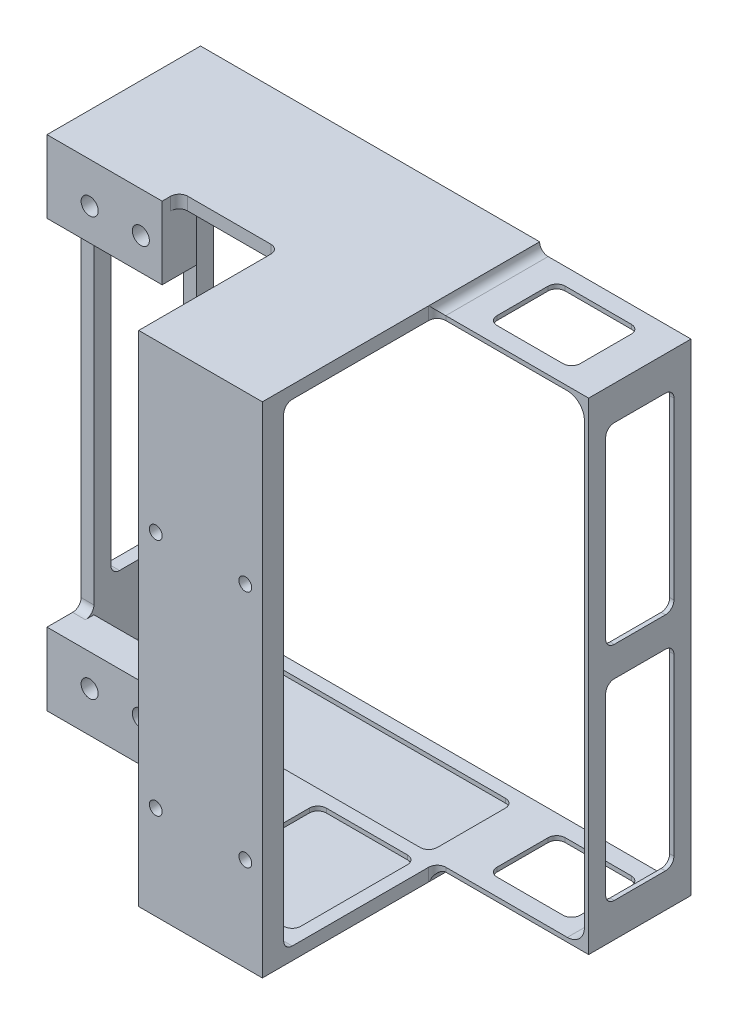
SolidWorks part; units mm, degrees
material "Bambu PETG HF"
ref_plane "Front Plane" through (0, 0, 0) normal (0, 0, 1) x (1, 0, 0)
ref_plane "Top Plane" through (0, 0, 0) normal (0, 1, 0) x (1, 0, 0)
ref_plane "Right Plane" through (0, 0, 0) normal (1, 0, 0) x (0, 0, -1)
sketch "Sketch2" plane through (0, 0, 0) normal (0, 0, 1) x (1, 0, 0)
  line L1 (-56.5, -56.5) -> (56.5, -56.5)
  line L2 (-56.5, -56.5) -> (-56.5, 56.5)
  line L3 (-56.5, 56.5) -> (56.5, 56.5)
  line L4 (56.5, -56.5) -> (56.5, 56.5)
  line L5 (-56.5, -56.5) -> (56.5, 56.5) construction
  line L6 (-56.5, 56.5) -> (56.5, -56.5) construction
  line L7 (-53.5, -53.5) -> (53.5, -53.5)
  line L8 (-53.5, -53.5) -> (-53.5, 53.5)
  line L9 (-53.5, 53.5) -> (53.5, 53.5)
  line L10 (53.5, -53.5) -> (53.5, 53.5)
  line L11 (-53.5, -53.5) -> (53.5, 53.5) construction
  line L12 (-53.5, 53.5) -> (53.5, -53.5) construction
  point P0 (0, 0)
  point P6 (0, 0)
  dimension "D1" = 3
  dimension "D2" = 107
  dimension "D4" = 107
extrude "Boss-Extrude1" add sketch "Sketch2" along normal blind 11
sketch "Sketch3" plane through (0, 0, 0) normal (0, 0, 1) x (1, 0, 0)
  line L0 (-56.5, 56.5) -> (-56.5, -56.5) construction
  line L2 (-56.5, 15) -> (-96.5, 15)
  line L3 (-56.5, 15) -> (-56.5, -15)
  line L4 (-56.5, -15) -> (-96.5, -15)
  line L5 (-96.5, 15) -> (-96.5, -15)
  point P6 (-56.5, 0)
  dimension "D1" = 30
  dimension "D2" = 40
extrude "Boss-Extrude2" add sketch "Sketch3" along normal blind 2
sketch "Sketch6" plane through (0, 0, 0) normal (0, 0, 1) x (1, 0, 0)
  line L0 (-56.5, -56.5) -> (56.5, -56.5) construction
  line L1 (-3, -56.5) -> (21, -56.5)
  line L2 (-3, -56.5) -> (-3, -58.5)
  line L3 (-3, -58.5) -> (21, -58.5)
  line L4 (21, -56.5) -> (21, -58.5)
  line L5 (-53.5, 0) -> (53.5, 0) construction
  line L6 (-53.5, 53.5) -> (-53.5, -53.5) construction
  line L7 (53.5, -53.5) -> (53.5, 53.5) construction
  line L8 (-3, 58.5) -> (21, 58.5)
  line L9 (21, 56.5) -> (21, 58.5)
  line L10 (-3, 56.5) -> (21, 56.5)
  line L11 (-3, 56.5) -> (-3, 58.5)
  line L12 (0, 0) -> (0, -53.5) construction
  line L13 (-53.5, -53.5) -> (53.5, -53.5) construction
  dimension "D1" = 2
  dimension "D2" = 24
  dimension "D3" = 3
extrude "Boss-Extrude5" add sketch "Sketch6" along normal blind 50 and the other way blind 10
sketch "Sketch8" plane through (0, 0, 50) normal (0, 0, 1) x (1, 0, 0)
  line L0 (-3, 58.5) -> (-8, 58.5)
  line L1 (-3, 58.5) -> (21, 58.5)
  line L3 (-3, -58.5) -> (21, -58.5)
  line L4 (21, 58.5) -> (21, -58.5)
  line L5 (-8, 58.5) -> (-8, -58.5)
  line L6 (-8, -58.5) -> (-3, -58.5)
  dimension "D1" = 24
  dimension "D2" = 5
extrude "Boss-Extrude6" add sketch "Sketch8" along normal blind 5
sketch "Sketch9" plane through (0, 0, 55) normal (0, 0, 1) x (1, 0, 0)
  line L0 (-3, 58.5) -> (-8, 58.5)
  line L5 (-3, -58.5) -> (21, -58.5)
  line L7 (21, 56.5) -> (21, 54.5)
  line L12 (-3, 58.5) -> (21, 58.5)
  line L14 (-8, 58.5) -> (-8, 43.5)
  line L15 (-8, 58.5) -> (-8, -58.5) construction
  line L16 (-8, 43.5) -> (21, 43.5)
  line L17 (21, -58.5) -> (21, 58.5) construction
  line L18 (21, 43.5) -> (21, 54.5)
  line L19 (45.8512, 0) -> (-63.6843, 0) construction
  line L20 (21, -43.5) -> (21, -54.5)
  line L21 (-8, -43.5) -> (21, -43.5)
  line L22 (-8, -58.5) -> (-8, -43.5)
  line L23 (-3, -58.5) -> (-8, -58.5)
  line L25 (21, -56.5) -> (21, -54.5)
  line L26 (21, 58.5) -> (21, 56.5)
  line L27 (21, -58.5) -> (21, -56.5)
  dimension "D1" = 15
extrude "Boss-Extrude7" add sketch "Sketch9" along normal blind 4
sketch "Sketch12" plane through (0, 0, 55) normal (0, 0, 1) x (1, 0, 0)
  line L0 (17, 19.5) -> (-4, 19.5) construction
  line L1 (17, -36.5) -> (-4, -36.5) construction
  line L2 (-8, 43.5) -> (-8, -43.5) construction
  line L4 (-8, -58.5) -> (21, -58.5) construction
  line L5 (6.5, 19.5) -> (6.5, -36.5) construction
  circle A0 centre (17, 19.5) radius 1.5
  circle A1 centre (-4, 19.5) radius 1.5
  circle A2 centre (17, -36.5) radius 1.5
  circle A3 centre (-4, -36.5) radius 1.5
  point P8 (6.5, -36.5)
  dimension "D1" = 56
  dimension "D2" = 21
  dimension "D3" = 22
  dimension "D4" = 4
extrude "Cut-Extrude1" cut sketch "Sketch12" against normal through all
sketch "Sketch17" plane through (-56.5, 0, 0) normal (-1, 0, 0) x (0, 0, 1)
  line L1 (-20.9734, 30.8852) -> (89.5007, 30.8852)
  line L2 (-20.9734, 30.8852) -> (-20.9734, -32.0731)
  line L3 (-20.9734, -32.0731) -> (89.5007, -32.0731)
  line L4 (89.5007, 30.8852) -> (89.5007, -32.0731)
extrude "removal of battery extension" cut sketch "Sketch17" along normal through all
sketch "Sketch18" plane through (0, 0, 0) normal (0, 0, -1) x (-1, 0, 0)
  line L1 (-56.5, -56.5) -> (56.5, -56.5)
  line L2 (-56.5, -56.5) -> (-56.5, 56.5)
  line L3 (-56.5, 56.5) -> (56.5, 56.5)
  line L4 (56.5, -56.5) -> (56.5, 56.5)
  line L5 (-56.5, -56.5) -> (56.5, 56.5) construction
  line L6 (-56.5, 56.5) -> (56.5, -56.5) construction
  line L7 (-53.5, -53.5) -> (53.5, -53.5)
  line L8 (-53.5, -53.5) -> (-53.5, 53.5)
  line L9 (-53.5, 53.5) -> (53.5, 53.5)
  line L10 (53.5, -53.5) -> (53.5, 53.5)
  line L11 (-53.5, -53.5) -> (53.5, 53.5) construction
  line L12 (-53.5, 53.5) -> (53.5, -53.5) construction
  point P0 (0, 0)
  point P7 (0, 0)
extrude "Extend walls" add sketch "Sketch18" along normal blind 10
sketch "Sketch22" plane through (0, 0, 11) normal (0, 0, 1) x (1, 0, 0)
  line L0 (21, 56.5) -> (-3, 56.5)
  line L1 (-3, 56.5) -> (-3, 53.5)
  line L2 (53.5, 53.5) -> (-53.5, 53.5) construction
  line L3 (-3, 53.5) -> (21, 53.5)
  line L4 (21, 53.5) -> (21, 56.5)
  line L5 (-3, -56.5) -> (21, -56.5)
  line L6 (21, -56.5) -> (21, -53.5)
  line L7 (-53.5, -53.5) -> (53.5, -53.5) construction
  line L8 (21, -53.5) -> (-3, -53.5)
  line L9 (-3, -53.5) -> (-3, -56.5)
extrude "Boss-Extrude10" add sketch "Sketch22" along normal up to next
sketch "Sketch23" plane through (0, 0, 11) normal (0, 0, 1) x (1, 0, 0)
  line L0 (21, -56.5) -> (21, -53.5)
  line L1 (21, -53.5) -> (53.5, -53.5)
  line L2 (53.5, -53.5) -> (53.5, 53.5)
  line L3 (53.5, 53.5) -> (21, 53.5)
  line L4 (21, 53.5) -> (21, 56.5)
  line L5 (21, 56.5) -> (56.5, 56.5)
  line L6 (56.5, 56.5) -> (56.5, -56.5)
  line L7 (56.5, -56.5) -> (21, -56.5)
  line L8 (-3, 53.5) -> (-3, 56.5)
  line L9 (-3, 56.5) -> (-56.5, 56.5)
  line L10 (-56.5, 56.5) -> (-56.5, -56.5)
  line L11 (-56.5, -56.5) -> (-3, -56.5)
  line L12 (-3, -56.5) -> (-3, -53.5)
  line L13 (-3, -53.5) -> (-53.5, -53.5)
  line L14 (-53.5, -53.5) -> (-53.5, 53.5)
  line L15 (-53.5, 53.5) -> (-3, 53.5)
extrude "Boss-Extrude11" add sketch "Sketch23" along normal blind 7
sketch "Sketch24" plane through (0, 0, 18) normal (0, 0, 1) x (1, 0, 0)
  line L0 (-56.5, 56.5) -> (-29.5, 56.5)
  line L1 (-3, 56.5) -> (-56.5, 56.5) construction
  line L2 (-29.5, 56.5) -> (-29.5, 41.5)
  line L3 (-29.5, 41.5) -> (-56.5, 41.5)
  line L4 (-56.5, 56.5) -> (-56.5, -56.5) construction
  line L5 (-56.5, 41.5) -> (-56.5, 56.5)
  line L6 (-108.2725, 0) -> (166.4714, 0) construction
  line L7 (-29.5, -41.5) -> (-56.5, -41.5)
  line L8 (-29.5, -56.5) -> (-29.5, -41.5)
  line L9 (-56.5, -56.5) -> (-29.5, -56.5)
  line L10 (-56.5, -41.5) -> (-56.5, -56.5)
  dimension "D1" = 15
  dimension "D2" = 27
extrude "Boss-Extrude12" add sketch "Sketch24" along normal blind 8
sketch "Sketch25" plane through (0, 0, 26) normal (0, 0, 1) x (1, 0, 0)
  line L0 (-58.2026, 49) -> (-24.3527, 49) construction
  line L1 (85.7624, 0) -> (-93.076, 0) construction
  line L3 (-56.5, 56.5) -> (-56.5, 41.5) construction
  circle A0 centre (-48.5, 49) radius 2
  circle A1 centre (-36.5, 49) radius 2
  circle A2 centre (-48.5, -49) radius 2
  circle A3 centre (-36.5, -49) radius 2
  dimension "D1" = 4
  dimension "D2" = 4
  dimension "D3" = 12
  dimension "D5" = 8
extrude "Cut-Extrude4" cut sketch "Sketch25" against normal blind 9
sketch "Sketch27" plane through (0, 56.5, 0) normal (0, 1, 0) x (1, 0, 0)
  line L0 (-29.5, -26) -> (-29.5, -18)
  line L1 (-29.5, -18) -> (-3, -18)
  line L2 (-3, -18) -> (-3, 10)
  line L3 (-3, 10) -> (-56.5, 10)
  line L4 (-56.5, 10) -> (-56.5, -26)
  line L5 (-56.5, -26) -> (-29.5, -26)
extrude "Boss-Extrude13" add sketch "Sketch27" along normal blind 2
sketch "Sketch28" plane through (0, -56.5, 0) normal (0, -1, 0) x (1, 0, 0)
  line L0 (-56.5, 26) -> (-56.5, -10)
  line L1 (-56.5, -10) -> (-3, -10)
  line L2 (-3, -10) -> (-3, 18)
  line L3 (-3, 18) -> (-29.5, 18)
  line L4 (-29.5, 18) -> (-29.5, 26)
  line L5 (-29.5, 26) -> (-56.5, 26)
extrude "Boss-Extrude14" add sketch "Sketch28" along normal blind 2
sketch "Sketch29" plane through (0, 0, 18) normal (0, 0, 1) x (1, 0, 0)
  line L0 (-3, 53.5) -> (-3, 58.5)
  line L1 (-3, 58.5) -> (-29.5, 58.5)
  line L2 (-29.5, 58.5) -> (-29.5, 53.5)
  line L3 (-29.5, 53.5) -> (-3, 53.5)
  line L4 (-79.818, 0) -> (91.158, 0) construction
  line L5 (-29.5, -58.5) -> (-29.5, -53.5)
  line L6 (-3, -58.5) -> (-29.5, -58.5)
  line L7 (-3, -53.5) -> (-3, -58.5)
  line L8 (-29.5, -53.5) -> (-3, -53.5)
extrude "Boss-Extrude15" add sketch "Sketch29" along normal blind 4
sketch "Sketch30" plane through (-56.5, 0, 0) normal (-1, 0, 0) x (0, 0, 1)
  line L0 (26, 58.5) -> (-10, 58.5)
  line L1 (-10, 58.5) -> (-10, -58.5)
  line L2 (-10, -58.5) -> (26, -58.5)
  line L3 (26, -58.5) -> (26, -41.5)
  line L4 (26, -41.5) -> (18, -41.5)
  line L5 (18, -41.5) -> (18, 41.5)
  line L6 (18, 41.5) -> (26, 41.5)
  line L7 (26, 41.5) -> (26, 58.5)
extrude "Boss-Extrude16" add sketch "Sketch30" along normal blind 2
sketch "Sketch31" plane through (0, 0, 50) normal (0, 0, -1) x (-1, 0, 0)
  line L0 (8, 58.5) -> (3, 58.5)
  line L1 (3, 58.5) -> (3, 53.5)
  line L2 (3, 53.5) -> (8, 53.5)
  line L3 (8, 58.5) -> (8, -58.5) construction
  line L4 (8, 53.5) -> (8, 58.5)
  line L5 (62.5415, 0) -> (-54.383, 0) construction
  line L6 (3, -53.5) -> (8, -53.5)
  line L7 (3, -58.5) -> (3, -53.5)
  line L8 (8, -58.5) -> (3, -58.5)
  line L9 (8, -53.5) -> (8, -58.5)
extrude "Boss-Extrude17" add sketch "Sketch31" along normal up to next
sketch "Sketch32" plane through (0, 0, 18) normal (0, 0, 1) x (1, 0, 0)
  line L0 (21, -56.5) -> (21, -53.5)
  line L1 (21, -53.5) -> (53.5, -53.5)
  line L2 (53.5, -53.5) -> (53.5, 53.5)
  line L3 (53.5, 53.5) -> (21, 53.5)
  line L4 (21, 53.5) -> (21, 56.5)
  line L5 (21, 56.5) -> (56.5, 56.5)
  line L6 (56.5, 56.5) -> (56.5, -56.5)
  line L7 (56.5, -56.5) -> (21, -56.5)
extrude "Cut-Extrude5" cut sketch "Sketch32" against normal blind 4
sketch "Sketch33" plane through (0, -43.5, 0) normal (0, 1, 0) x (1, 0, 0)
  line L0 (21, -59) -> (21, -55)
  line L1 (21, -55) -> (-8, -55)
  line L2 (-8, -55) -> (-8, -59)
  line L3 (-8, -59) -> (21, -59)
extrude "Cut-Extrude6" cut sketch "Sketch33" against normal mid plane 220
sketch "Sketch34" plane through (56.5, 0, 0) normal (1, 0, 0) x (0, 0, -1)
  line L0 (30.1438, 0) -> (-36.494, 0) construction
  line L1 (-2, -56.5) -> (-2, 56.5) construction
  line L2 (-14, -56.5) -> (10, -56.5) construction
  line L3 (-14, 56.5) -> (10, 56.5) construction
  line L4 (-2, -48.5) -> (-10, -48.5)
  line L5 (-10, -48.5) -> (-10, -3.5)
  line L6 (-10, -3.5) -> (6, -3.5)
  line L7 (6, -3.5) -> (6, -48.5)
  line L8 (6, -48.5) -> (-2, -48.5)
  line L9 (-14, -56.5) -> (-14, 56.5) construction
  line L10 (10, 56.5) -> (10, -56.5) construction
  line L11 (6, 3.5) -> (6, 48.5)
  line L12 (6, 48.5) -> (-2, 48.5)
  line L13 (-2, 48.5) -> (-10, 48.5)
  line L14 (-10, 48.5) -> (-10, 3.5)
  line L15 (-10, 3.5) -> (6, 3.5)
  dimension "D1" = 45
  dimension "D2" = 8
  dimension "D3" = 4
  dimension "D4" = 4
extrude "Cut-Extrude7" cut sketch "Sketch34" against normal blind 10
sketch "Sketch35" plane through (0, -56.5, 0) normal (0, -1, 0) x (1, 0, 0)
  line L0 (56.5, 2) -> (21, 2) construction
  line L1 (56.5, 14) -> (56.5, -10) construction
  line L2 (21, -10) -> (21, 14) construction
  line L3 (38.75, 14) -> (38.75, -10) construction
  line L4 (21, 14) -> (56.5, 14) construction
  line L5 (56.5, -10) -> (21, -10) construction
  line L7 (29, 10) -> (48.5, 10)
  line L8 (29, 10) -> (29, -6)
  line L9 (29, -6) -> (48.5, -6)
  line L10 (48.5, 10) -> (48.5, -6)
  line L11 (29, 10) -> (48.5, -6) construction
  line L12 (29, -6) -> (48.5, 10) construction
  point P12 (38.75, 2)
  dimension "D1" = 8
  dimension "D2" = 4
extrude "Cut-Extrude8" cut sketch "Sketch35" against normal through all
sketch "Sketch37" plane through (-29.5, 0, 0) normal (1, 0, 0) x (0, 0, -1)
  line L0 (-26, 41.5) -> (-26, 58.5) construction
  line L1 (-22, -58.5) -> (-26, -58.5)
  line L2 (-22, -58.5) -> (-22, 58.5)
  line L3 (-22, 58.5) -> (-26, 58.5)
  line L4 (-26, -58.5) -> (-26, 58.5)
  line L5 (-26, 58.5) -> (-22, 58.5) construction
extrude "Cut-Extrude13" cut sketch "Sketch37" against normal blind 2
sketch "Sketch38" plane through (0, 0, 22) normal (0, 0, 1) x (1, 0, 0)
  line L0 (-29.5, -41.5) -> (-31.5, -41.5)
  line L1 (-29.5, -41.5) -> (-29.5, -53.5)
  line L2 (-29.5, -53.5) -> (-31.5, -53.5)
  line L3 (-31.5, -58.5) -> (-31.5, -41.5) construction
  line L4 (-31.5, -53.5) -> (-31.5, -41.5)
  line L5 (-67.9912, 0) -> (83.8266, 0) construction
  line L6 (-29.5, 53.5) -> (-31.5, 53.5)
  line L7 (-31.5, 53.5) -> (-31.5, 41.5)
  line L8 (-29.5, 41.5) -> (-31.5, 41.5)
  line L9 (-29.5, 41.5) -> (-29.5, 53.5)
extrude "Cut-Extrude14" cut sketch "Sketch38" against normal blind 10
fillet "Fillet1" radius 2 36 edges at (-42.5, 53.5, 18) (-42.5, -53.5, 18) (-56, -41.5, 18) (-56, 41.5, 18) (-31.5, 53.5, 20) (-31.5, 56, 22) (-31.5, -53.5, 20) (-31.5, -56, 22) (-53.5, -53.5, 4) (-53.5, 53.5, 4) (53.5, 53.5, 2) (53.5, -53.5, 2) (48.5, -55, 10) (48.5, -55, -6) (29, -55, 10) (29, -55, -6) (55, -48.5, -6) (55, -3.5, -6) (55, -3.5, 10) (55, -48.5, 10) (55, 3.5, 10) (55, 3.5, -6) (55, 48.5, 10) (55, 48.5, -6) (29, 55, -6) (48.5, 55, -6) (48.5, 55, 10) (29, 55, 10) (21, 56.5, 2) (21, 55, 14) (21, -56.5, 2) (21, -55, 14) (6.5, 53.5, 50) (6.5, -53.5, 50) (-8, 56, 22) (-8, -56, 22)
sketch "Sketch39" plane through (-58.5, 0, 0) normal (-1, 0, 0) x (0, 0, 1)
  line L0 (-10, 41.5) -> (20, 41.5) construction
  line L1 (-10, 58.5) -> (-10, -58.5) construction
  line L2 (20, -41.5) -> (-10, -41.5) construction
  line L3 (14, -0.7156) -> (14, -35.5)
  line L4 (14, -35.5) -> (-6, -35.5)
  line L5 (-6, -35.5) -> (-6, 35.5)
  line L6 (-6, 35.5) -> (14, 35.5)
  line L7 (14, 35.5) -> (14, -0.7156)
  line L8 (18, -39.5) -> (18, 39.5) construction
  dimension "D1" = 6
  dimension "D2" = 6
  dimension "D3" = 4
  dimension "D4" = 4
extrude "Cut-Extrude15" cut sketch "Sketch39" against normal blind 10
fillet "Fillet2" radius 2 4 edges at (-56, -35.5, -6) (-56, -35.5, 14) (-56, 35.5, -6) (-56, 35.5, 14)
sketch "Sketch40" plane through (0, 0, 0) normal (0, 1, 0) x (1, 0, 0)
  line L0 (-8, -48) -> (21, -48) construction
  line L1 (21, -48) -> (21, -13) construction
  line L2 (21, -16) -> (21, -55) construction
  line L3 (21, -13) -> (-8, -13) construction
  line L4 (-8, -13) -> (-8, -48) construction
  line L6 (-51.5, -16) -> (21, -16) construction
  line L7 (21, -48) -> (-8, -13) construction
  line L9 (21, -16) -> (21, 10) construction
  line L10 (-8, -48) -> (21, -13) construction
  line L12 (21, 10) -> (-51.5, 10) construction
  line L13 (-51.5, 10) -> (-51.5, -16) construction
  line L14 (-5, -45) -> (18, -45)
  line L15 (-5, -45) -> (-5, -16)
  line L16 (-5, -16) -> (18, -16)
  line L17 (18, -45) -> (18, -16)
  line L18 (-5, -45) -> (18, -16) construction
  line L19 (-5, -16) -> (18, -45) construction
  line L24 (21, -16) -> (-51.5, 10) construction
  line L26 (-51.5, -16) -> (21, 10) construction
  line L27 (18, -13) -> (-48.5, -13)
  line L28 (18, -13) -> (18, 7)
  line L29 (18, 7) -> (-48.5, 7)
  line L30 (-48.5, -13) -> (-48.5, 7)
  line L31 (18, -13) -> (-48.5, 7) construction
  line L32 (18, 7) -> (-48.5, -13) construction
  point P10 (6.5, -30.5)
  point P12 (-15.25, -3.0328)
  point P18 (-15.25, -3)
  dimension "D1" = 3
  dimension "D2" = 3
  dimension "D3" = 3
  dimension "D4" = 3
  dimension "D5" = 20
  dimension "D6" = 29
extrude "Cut-Extrude16" cut sketch "Sketch40" against normal mid plane 113
fillet "Fillet3" radius 2 15 edges at (-5, 55, 16) (-5, 55, 45) (18, 55, 45) (18, 55, 13) (18, 55, -7) (-48.5, 55, -7) (-48.5, 55, 13) (18, -55, -7) (18, -55, 13) (-48.5, -55, -7) (-48.5, -55, 13) (-5, -55, 16) (-5, -55, 45) (18, -55, 16) (18, -55, 45)
fillet "Fillet4" radius 2 1 edges at (18, 55, 16)
ref_plane "Plane1" through (0, 0, 18) normal (0, 0, -1) x (-1, 0, 0)
sketch "Sketch42" plane through (0, 0, 18) normal (0, 0, -1) x (-1, 0, 0)
  line L0 (53.5, -51.5) -> (53.5, 51.5) construction
  line L1 (-51.5, -53.5) -> (51.5, -53.5) construction
  line L2 (-53.5, 51.5) -> (-53.5, -51.5) construction
  line L3 (53.5, -51.5) -> (53.5, 51.5)
  line L4 (-51.5, -53.5) -> (51.5, -53.5)
  line L5 (-53.5, 51.5) -> (-53.5, -51.5)
  line L6 (51.5, 53.5) -> (-51.5, 53.5) construction
  line L7 (51.5, 53.5) -> (-51.5, 53.5)
  line L8 (-55.5, 51.5) -> (-55.5, -51.5)
  line L9 (-51.5, -55.5) -> (51.5, -55.5)
  line L10 (55.5, -51.5) -> (55.5, 51.5)
  line L11 (51.5, 55.5) -> (-51.5, 55.5)
  arc A0 (-51.5, 53.5) -> (-53.5, 51.5) centre (-51.5, 51.5) ccw construction
  arc A1 (53.5, 51.5) -> (51.5, 53.5) centre (51.5, 51.5) ccw construction
  arc A2 (51.5, -53.5) -> (53.5, -51.5) centre (51.5, -51.5) ccw construction
  arc A3 (-53.5, -51.5) -> (-51.5, -53.5) centre (-51.5, -51.5) ccw construction
  arc A4 (-51.5, 53.5) -> (-53.5, 51.5) centre (-51.5, 51.5) ccw
  arc A5 (53.5, 51.5) -> (51.5, 53.5) centre (51.5, 51.5) ccw
  arc A6 (51.5, -53.5) -> (53.5, -51.5) centre (51.5, -51.5) ccw
  arc A7 (-53.5, -51.5) -> (-51.5, -53.5) centre (-51.5, -51.5) ccw
  arc A8 (-55.5, -51.5) -> (-51.5, -55.5) centre (-51.5, -51.5) ccw
  arc A9 (51.5, -55.5) -> (55.5, -51.5) centre (51.5, -51.5) ccw
  arc A10 (55.5, 51.5) -> (51.5, 55.5) centre (51.5, 51.5) ccw
  arc A11 (-51.5, 55.5) -> (-55.5, 51.5) centre (-51.5, 51.5) ccw
  dimension "D1" = 2
  dimension "D2" = 2
extrude "Cut-Extrude20" cut sketch "Sketch42" along normal blind 63 contours L8 A8 L9 A9 L10 A10 L11 A11
sketch "Sketch44" plane through (0, 0, 18) normal (0, 0, -1) x (-1, 0, 0)
  line L0 (55.5, 41.5) -> (55.5, -41.5)
  line L1 (55.5, 39.5) -> (55.5, 51.5) construction
  line L2 (55.5, -51.5) -> (55.5, -39.5) construction
  line L3 (55.5, -41.5) -> (31.5, -41.5)
  line L4 (31.5, -41.5) -> (53.5, -41.5) construction
  line L5 (5, -55.5) -> (51.5, -55.5) construction
  line L7 (31.5, -41.5) -> (31.5, -55.5)
  line L8 (31.5, -55.5) -> (-21, -55.5)
  line L9 (-21, -55.5) -> (-21, 55.5)
  line L12 (31.5, 53.5) -> (31.5, 41.5)
  line L13 (31.5, 41.5) -> (55.5, 41.5)
  line L14 (-21, 55.5) -> (31.5, 55.5)
  line L15 (51.5, 55.5) -> (5, 55.5) construction
  line L16 (31.5, 55.5) -> (31.5, 53.5)
  dimension "D1" = 90
extrude "Cut-Extrude21" cut sketch "Sketch44" against normal up to vertex (32 mm away) up to point (-8, 51.5, 50)
fillet "Fillet6" radius 2 2 edges at (6.5, -55.5, 50) (6.5, 55.5, 50)
